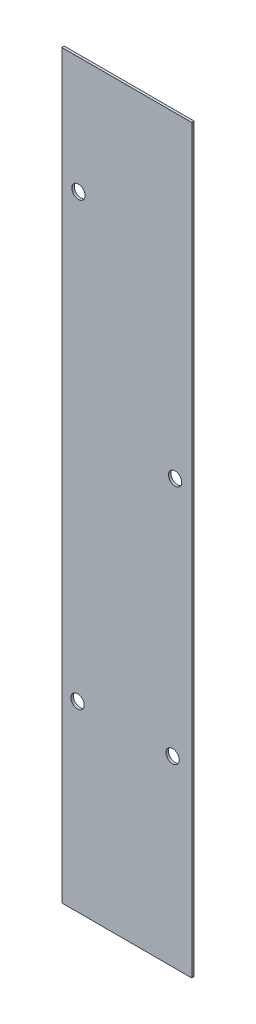
SolidWorks part; units mm, degrees
material "Acrylic (Medium-high impact)"
ref_plane "Front Plane" through (0, 0, 0) normal (0, 0, 1) x (1, 0, 0)
ref_plane "Top Plane" through (0, 0, 0) normal (0, 1, 0) x (1, 0, 0)
ref_plane "Right Plane" through (0, 0, 0) normal (1, 0, 0) x (0, 0, -1)
sketch "Sketch1" plane through (0, 0, 0) normal (0, 0, 1) x (1, 0, 0)
  line L1 (0, 222.25) -> (39, 222.25)
  line L2 (0, 222.25) -> (0, 0)
  line L3 (0, 0) -> (39, 0)
  line L4 (39, 222.25) -> (39, 0)
  dimension "D1" = 222.25
  dimension "D2" = 39
base flange "Base-Flange1" sketch "Sketch1" thickness 0.7366 reverse thickness direction no parameters "D1"=0.7366
sketch "Sketch2" plane through (0, 0, 0) normal (0, 0, 1) x (1, 0, 0)
  circle A0 centre (5, 187.25) radius 1.9844 construction
  circle A1 centre (34, 127.25) radius 1.9844 construction
  circle A2 centre (4.7366, 54.75) radius 1.9844 construction
  circle A3 centre (33.2634, 54.75) radius 1.9844 construction
  circle A4 centre (5, 187.25) radius 1.9844
  circle A5 centre (34, 127.25) radius 1.9844
  circle A6 centre (4.7366, 54.75) radius 1.9844
  circle A7 centre (33.2634, 54.75) radius 1.9844
extrude "Cut-Extrude1" cut sketch "Sketch2" against normal blind 10 normal cut yes
sketch "Bend-Lines1" [suppressed] plane through (0, 0, 0) normal (0, 1, 0) x (1, 0, 0)
sketch "Bounding-Box1" [suppressed] plane through (0, 0, 0) normal (0, 1, 0) x (1, 0, 0)
sheet metal parameters "Sheet-Metal3" thickness 0.7366 parameters "D1"=0.7366
flat pattern "Flat-Pattern3" [suppressed]
sketch "Bend-Lines2" plane through (0, 0, 0) normal (0, 1, 0) x (1, 0, 0)
sketch "Bounding-Box2" [suppressed] plane through (0, 0, 0) normal (0, 1, 0) x (1, 0, 0)
sheet metal parameters "Sheet-Metal4" thickness 0.7366 parameters "D1"=0.7366
flat pattern "Flat-Pattern3"
sketch "Bend-Lines2" plane through (0, 0, 0) normal (0, 1, 0) x (1, 0, 0)
sketch3d "Bounding-Box2" [suppressed]
  line L0 (39, 222.25, 0) -> (39, 0, 0) construction
  line L1 (0, 222.25, 0) -> (0, 0, 0) construction
  line L2 (39, 222.25, 0) -> (0, 222.25, 0) construction
  line L3 (39, 0, 0) -> (0, 0, 0) construction
